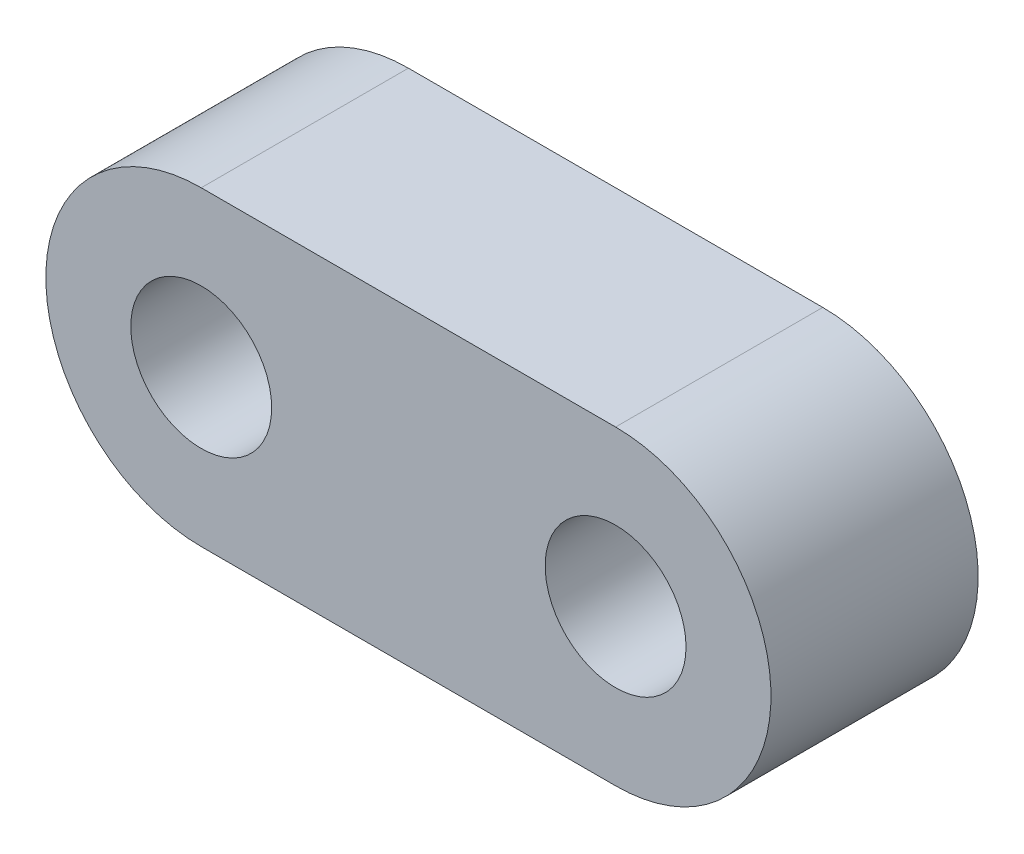
SolidWorks part; units mm, degrees
ref_plane "Front Plane" through (0, 0, 0) normal (0, 0, 1) x (1, 0, 0)
ref_plane "Top Plane" through (0, 0, 0) normal (0, 1, 0) x (1, 0, 0)
ref_plane "Right Plane" through (0, 0, 0) normal (1, 0, 0) x (0, 0, -1)
sketch "Sketch1" plane through (0, 0, 0) normal (0, 0, 1) x (1, 0, 0)
  line L0 (0, 0) -> (12.7, 0) construction
  line L1 (0, 4.7625) -> (12.7, 4.7625)
  line L2 (0, -4.7625) -> (12.7, -4.7625)
  arc A0 (0, 4.7625) -> (0, -4.7625) centre (0, 0) ccw
  arc A1 (12.7, -4.7625) -> (12.7, 4.7625) centre (12.7, 0) ccw
  circle A2 centre (12.7, 0) radius 2.159
  circle A3 centre (0, 0) radius 2.159
  point P3 (6.35, 0)
  dimension "D2" = 9.525
  dimension "D3" = 4.318
  dimension "D1" = 12.7
extrude "Boss-Extrude1" add sketch "Sketch1" along normal blind 6.35
sketch "Sketch2" plane through (0, 0, 6.35) normal (0, 0, 1) x (1, 0, 0)
  point P0 (0, 0)
